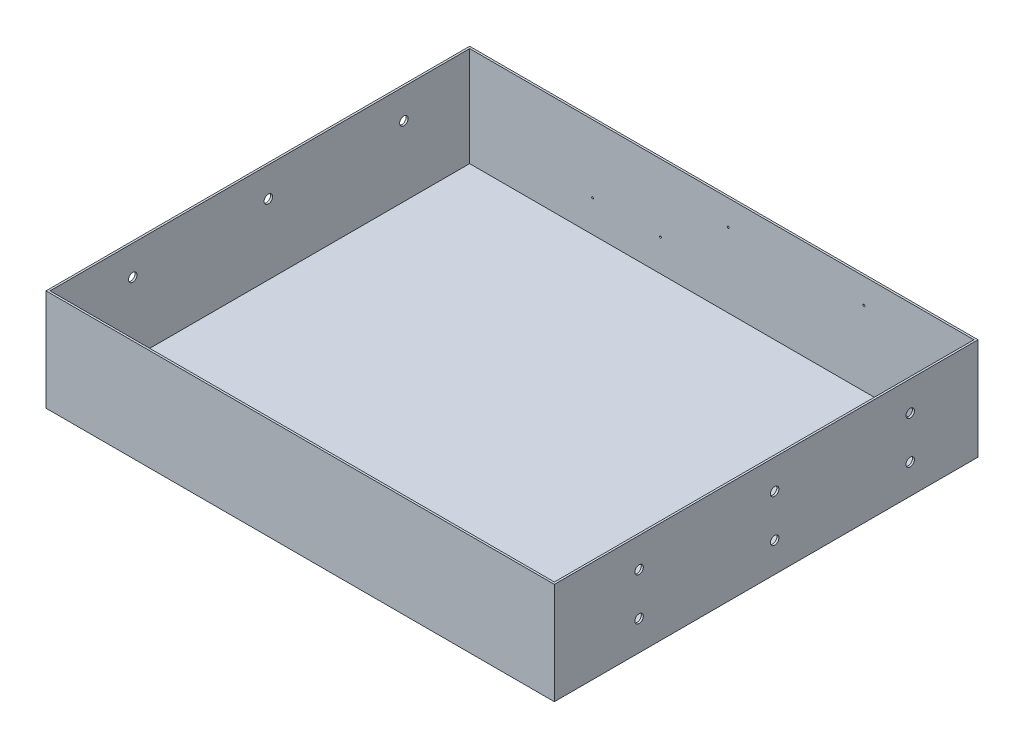
SolidWorks part; units mm, degrees
material "6061 Alloy"
ref_plane "Front Plane" through (0, 0, 0) normal (0, 0, 1) x (1, 0, 0)
ref_plane "Top Plane" through (0, 0, 0) normal (0, 1, 0) x (1, 0, 0)
ref_plane "Right Plane" through (0, 0, 0) normal (1, 0, 0) x (0, 0, -1)
sketch "Sketch1" plane through (0, 0, 0) normal (0, 1, 0) x (1, 0, 0)
  line L1 (-508, 508) -> (254, 508)
  line L2 (-508, 508) -> (-508, -127)
  line L3 (-508, -127) -> (254, -127)
  line L4 (254, 508) -> (254, -127)
  dimension "D1" = 508
  dimension "D2" = 635
  dimension "D3" = 762
  dimension "D4" = 508
extrude "Extrude1" add sketch "Sketch1" along normal blind 152.4
shell "Shell1" thickness 3.048 removed face at (-127, 152.4, -190.5)
sketch "Sketch2" plane through (-508, 0, 0) normal (-1, 0, 0) x (0, 0, 1)
  line L0 (-508, 152.4) -> (-508, 0) construction
  line L1 (-504.952, 152.4) -> (123.952, 152.4) construction
  circle A0 centre (-406.4, 107.95) radius 6.35
  dimension "D1" = 12.7
  dimension "D2" = 101.6
  dimension "D3" = 44.45
extrude "Connector mount--Cut-Extrude1" cut sketch "Sketch2" against normal through all
pattern_linear "LPattern1" count 3 spacing 203.2 along (0, 0, 1) of face at (-504.952, 107.95, -412.75)
pattern_linear "LPattern5" count 3 spacing 203.2 along (0, 0, 1) count 2 spacing 63.5 along (0, -1, 0) of face at (250.952, 107.95, -400.05)
sketch "Sketch3" plane through (0, 0, -508) normal (0, 0, -1) x (-1, 0, 0)
  line L0 (-250.952, 152.4) -> (-250.952, 3.048) construction
  line L1 (-250.952, 152.4) -> (504.952, 152.4) construction
  circle A0 centre (-85.852, 114.3) radius 1.524
  dimension "D1" = 3.048
  dimension "D3" = 38.1
  dimension "D2" = 165.1
extrude "Clip Mount --Cut-Extrude2" cut sketch "Sketch3" against normal blind 39.624
pattern_linear "LPattern2" count 5 spacing 101.6 along (-1, 0, 0) count 2 spacing 63.5 along (0, -1, 0) skipping (0, 1), (1, 0), (1, 1), (2, 1), (3, 0), (4, 0) of face at (87.376, 114.3, -504.952)
sketch "Sketch4" plane through (0, 0, 127) normal (0, 0, 1) x (1, 0, 0)
  circle A0 centre (-411.3748, 76.774) radius 6.35
  dimension "D1" = 12.7
extrude "Lower Connector Mnt--Cut-Extrude1" [suppressed] cut sketch "Sketch4" against normal up to surface (3.048 mm away) up to face at (-127, 77.724, 123.952)
pattern_linear "LPattern3" [suppressed] count 3 spacing 228.6 of bodies 106
sketch "Sketch5" plane through (0, 3.048, 0) normal (0, 1, 0) x (-1, 0, 0)
  line L0 (-250.952, 123.952) -> (-250.952, -504.952) construction
  line L1 (-250.952, -504.952) -> (504.952, -504.952) construction
  circle A0 centre (-111.252, -327.152) radius 1.524
  dimension "D1" = 3.048
  dimension "D2" = 139.7
  dimension "D3" = 177.8
extrude "Cut-Extrude1" [suppressed] cut sketch "Sketch5" against normal up to surface (3.048 mm away) up to face at (-127, 0, -190.5)
pattern_linear "LPattern4" [suppressed] count 3 spacing 127 count 5 spacing 127 of bodies 108
